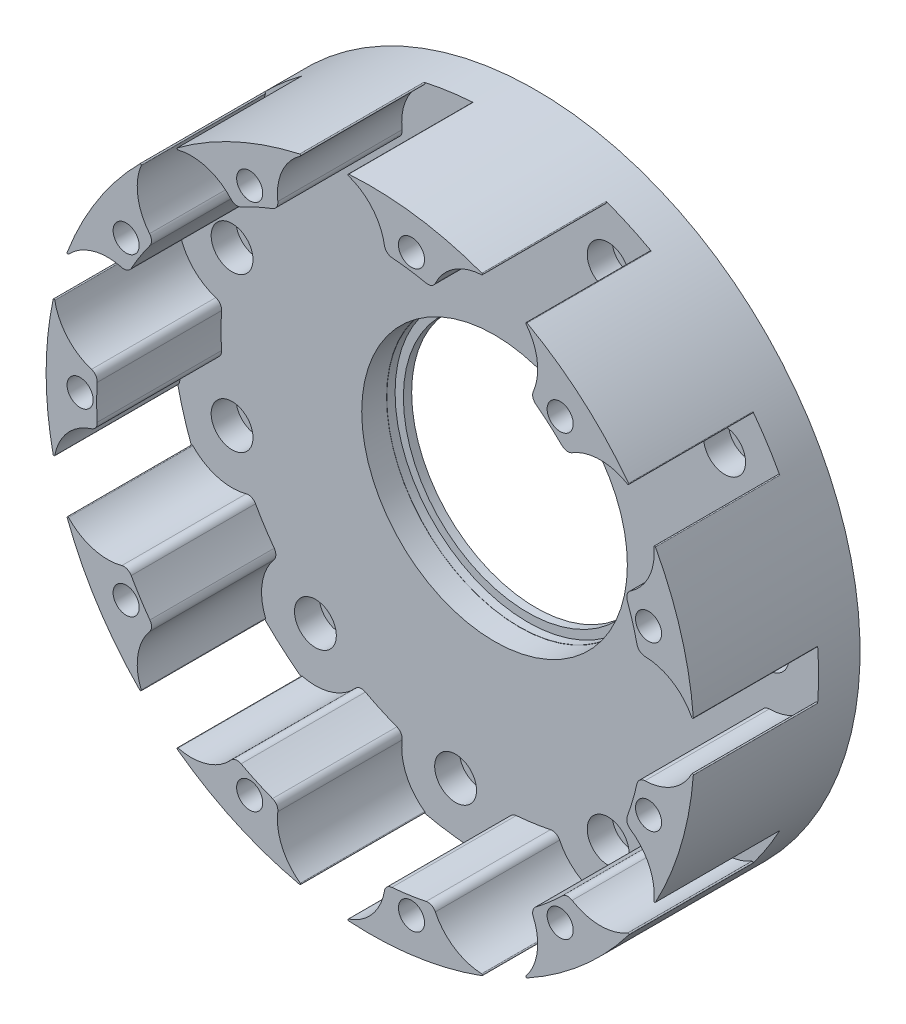
SolidWorks part; units mm, degrees
material "ABS"
ref_plane "Front Plane" through (0, 0, 0) normal (0, 0, 1) x (1, 0, 0)
ref_plane "Top Plane" through (0, 0, 0) normal (0, 1, 0) x (1, 0, 0)
ref_plane "Right Plane" through (0, 0, 0) normal (1, 0, 0) x (0, 0, -1)
sketch "Sketch1" plane through (0, 0, 0) normal (0, 0, 1) x (1, 0, 0)
  circle A0 centre (0, 0) radius 39.1
  circle A1 centre (0, 0) radius 33 construction
  circle A2 centre (33, 0) radius 2.525
  circle A3 centre (27.7614, -17.8411) radius 2.525
  circle A4 centre (13.7087, -30.0179) radius 2.525
  circle A5 centre (-4.6964, -32.6641) radius 2.525
  circle A6 centre (-21.6104, -24.9397) radius 2.525
  circle A7 centre (-31.6633, -9.2972) radius 2.525
  circle A8 centre (-31.6633, 9.2972) radius 2.525
  circle A9 centre (-21.6104, 24.9397) radius 2.525
  circle A10 centre (-4.6964, 32.6641) radius 2.525
  circle A11 centre (13.7087, 30.0179) radius 2.525
  circle A12 centre (27.7614, 17.8411) radius 2.525
  circle A13 centre (0, 0) radius 16.025
  point P28 (0, 0)
extrude "Boss-Extrude1" add sketch "Sketch1" along normal blind 3
sketch "Sketch2" plane through (0, 0, 0) normal (0, 0, -1) x (-1, 0, 0)
  circle A0 centre (0, 0) radius 16
  circle A1 centre (0, 0) radius 39.1
  circle A2 centre (0, 0) radius 39.1 construction
  dimension "D1" = 32
extrude "Boss-Extrude2" add sketch "Sketch2" along normal blind 2 contours A1 | A0
sketch "Sketch3" plane through (0, 0, 3) normal (0, 0, 1) x (1, 0, 0)
  circle A0 centre (33, 0) radius 1.6
  circle A1 centre (27.7614, -17.8411) radius 1.6
  circle A2 centre (13.7087, -30.0179) radius 1.6
  circle A3 centre (-4.6964, -32.6641) radius 1.6
  circle A4 centre (-21.6104, -24.9397) radius 1.6
  circle A5 centre (-31.6633, -9.2972) radius 1.6
  circle A6 centre (-31.6633, 9.2972) radius 1.6
  circle A7 centre (-21.6104, 24.9397) radius 1.6
  circle A8 centre (-4.6964, 32.6641) radius 1.6
  circle A9 centre (13.7087, 30.0179) radius 1.6
  circle A10 centre (27.7614, 17.8411) radius 1.6
  point P25 (0, 0)
  dimension "D1" = 3.2
  dimension "D2" = 11
sketch "Sketch4" plane through (0, 0, -2) normal (0, 0, -1) x (-1, 0, 0)
  circle A0 centre (0, 0) radius 16
  circle A1 centre (0, 0) radius 15
  dimension "D1" = 32
  dimension "D2" = 30
extrude "Boss-Extrude3" add sketch "Sketch4" against normal blind 1
sketch "Sketch5" plane through (0, 0, 3) normal (0, 0, 1) x (1, 0, 0)
  circle A0 centre (0, 0) radius 39.1
  circle A1 centre (0, 0) radius 39.1 construction
  arc A2 (1.7973, 32.951) -> (-11.0078, 31.1099) centre (-4.6964, 32.6641) ccw
  arc A3 (19.3266, 26.7485) -> (7.5589, 32.1226) centre (13.7087, 30.0179) ccw
  arc A4 (30.7199, 12.0535) -> (23.7258, 22.9366) centre (27.7614, 17.8411) ccw
  arc A5 (32.3598, -6.4684) -> (32.3598, 6.4684) centre (33, 0) ccw
  arc A6 (23.7258, -22.9366) -> (30.7199, -12.0535) centre (27.7614, -17.8411) ccw
  arc A7 (7.5589, -32.1226) -> (19.3266, -26.7485) centre (13.7087, -30.0179) ccw
  arc A8 (-11.0078, -31.1099) -> (1.7973, -32.951) centre (-4.6964, -32.6641) ccw
  arc A9 (-26.0797, -20.22) -> (-16.3027, -28.6918) centre (-21.6104, -24.9397) ccw
  arc A10 (-32.8714, -2.9104) -> (-29.2267, -15.3232) centre (-31.6633, -9.2972) ccw
  arc A11 (-29.2267, 15.3232) -> (-32.8714, 2.9104) centre (-31.6633, 9.2972) ccw
  arc A12 (-16.3027, 28.6918) -> (-26.0797, 20.22) centre (-21.6104, 24.9397) ccw
  arc A13 (-32.8714, 2.9104) -> (-32.8714, -2.9104) centre (0, 0) ccw
  arc A14 (-26.0797, 20.22) -> (-29.2267, 15.3232) centre (0, 0) ccw
  arc A15 (-11.0078, 31.1099) -> (-16.3027, 28.6918) centre (0, 0) ccw
  arc A16 (7.5589, 32.1226) -> (1.7973, 32.951) centre (0, 0) ccw
  arc A17 (23.7258, 22.9366) -> (19.3266, 26.7485) centre (0, 0) ccw
  arc A18 (32.3598, 6.4684) -> (30.7199, 12.0535) centre (0, 0) ccw
  arc A19 (30.7199, -12.0535) -> (32.3598, -6.4684) centre (0, 0) ccw
  arc A20 (19.3266, -26.7485) -> (23.7258, -22.9366) centre (0, 0) ccw
  arc A21 (1.7973, -32.951) -> (7.5589, -32.1226) centre (0, 0) ccw
  arc A22 (-16.3027, -28.6918) -> (-11.0078, -31.1099) centre (0, 0) ccw
  arc A23 (-29.2267, -15.3232) -> (-26.0797, -20.22) centre (0, 0) ccw
  point P29 (0, 0)
  point P30 (0, 0)
  point P42 (0, 0)
  dimension "D1" = 11
  dimension "D2" = 6.5
extrude "Boss-Extrude4" add sketch "Sketch5" along normal blind 15 contours A17 A4 A0 A3 | A18 A5 A0 A4 | A19 A6 A0 A5 | A20 A7 A0 A6 | A21 A8 A0 A7 | A22 A9 A0 A8 | A23 A10 A0 A9 | A13 A11 A0 A10 | A14 A12 A0 A11 | A15 A2 A0 A12 | A16 A3 A0 A2 region at (34.9977, 10.2762, 3) region at (34.9977, -10.2762, 3) region at (23.8862, 27.5661, 3) region at (23.8862, -27.5661, 3) region at (5.191, 36.1039, 3) region at (5.191, -36.1039, 3) region at (-15.1523, 33.179, 3) region at (-15.1523, -33.179, 3) region at (-30.6849, 19.72, 3) region at (-30.6849, -19.72, 3) region at (-36.4752, 0, 3)
fillet "Fillet1" radius 0.1 22 edges at (-7.9713, 38.2788, 10.5) (-27.401, 27.8926, 10.5) (-23.7091, 31.0916, 10.5) (-36.7548, 13.3378, 10.5) (-38.131, 8.6507, 10.5) (-38.131, -8.6507, 10.5) (-36.7548, -13.3378, 10.5) (-27.401, -27.8926, 10.5) (-23.7091, -31.0916, 10.5) (-7.9713, -38.2788, 10.5) (-3.136, -38.974, 10.5) (13.9892, -36.5118, 10.5) (18.4328, -34.4825, 10.5) (31.5083, -23.1525, 10.5) (34.1493, -19.043, 10.5) (39.0236, -2.4425, 10.5) (34.1493, 19.043, 10.5) (39.0236, 2.4425, 10.5) (31.5083, 23.1525, 10.5) (18.4328, 34.4825, 10.5) (13.9892, 36.5118, 10.5) (-3.136, 38.974, 10.5)
fillet "Fillet2" radius 1 22 edges at (-11.0078, -31.1099, 10.5) (-16.3027, -28.6918, 10.5) (23.7258, -22.9366, 10.5) (19.3266, -26.7485, 10.5) (7.5589, -32.1226, 10.5) (1.7973, -32.951, 10.5) (-29.2267, -15.3232, 10.5) (-26.0797, -20.22, 10.5) (-32.8714, -2.9104, 10.5) (-32.8714, 2.9104, 10.5) (-26.0797, 20.22, 10.5) (-29.2267, 15.3232, 10.5) (-16.3027, 28.6918, 10.5) (-11.0078, 31.1099, 10.5) (30.7199, -12.0535, 10.5) (32.3598, -6.4684, 10.5) (32.3598, 6.4684, 10.5) (30.7199, 12.0535, 10.5) (23.7258, 22.9366, 10.5) (19.3266, 26.7485, 10.5) (7.5589, 32.1226, 10.5) (1.7973, 32.951, 10.5)
sketch "Sketch7" plane through (0, 0, -2) normal (0, 0, -1) x (-1, 0, 0)
  line L0 (0, 0) -> (35, 0) construction
  circle A0 centre (35, 0) radius 1.575
  circle A1 centre (29.4439, -18.9224) radius 1.575
  circle A2 centre (14.5395, -31.8371) radius 1.575
  circle A3 centre (-4.981, -34.6438) radius 1.575
  circle A4 centre (-22.9201, -26.4512) radius 1.575
  circle A5 centre (-33.5823, -9.8606) radius 1.575
  circle A6 centre (-33.5823, 9.8606) radius 1.575
  circle A7 centre (-22.9201, 26.4512) radius 1.575
  circle A8 centre (-4.981, 34.6438) radius 1.575
  circle A9 centre (14.5395, 31.8371) radius 1.575
  circle A10 centre (29.4439, 18.9224) radius 1.575
  point P5 (0, 0)
  point P6 (0, 0)
  point P26 (0, 0)
  point P27 (0, 0)
  point P28 (0, 0)
  point P29 (0, 0)
  point P30 (0, 0)
  point P31 (0, 0)
  dimension "D2" = 3.15
  dimension "D1" = 35
  dimension "D3" = 11
extrude "Cut-Extrude1" cut sketch "Sketch7" against normal through all
sketch "Sketch8" plane through (0, 0, -2) normal (0, 0, -1) x (-1, 0, 0)
  line L0 (32.2124, -20.7016) -> (32.3689, -17.4145)
  line L1 (38.2909, 0) -> (36.6454, 2.85)
  line L2 (36.6454, 2.85) -> (33.3546, 2.85)
  line L3 (33.3546, 2.85) -> (31.7091, 0)
  line L4 (31.7091, 0) -> (33.3546, -2.85)
  line L5 (33.3546, -2.85) -> (36.6454, -2.85)
  line L6 (36.6454, -2.85) -> (38.2909, 0)
  line L7 (32.3689, -17.4145) -> (29.6005, -15.6353)
  line L8 (29.6005, -15.6353) -> (26.6754, -17.1432)
  line L9 (26.6754, -17.1432) -> (26.5188, -20.4304)
  line L10 (26.5188, -20.4304) -> (29.2873, -22.2096)
  line L11 (29.2873, -22.2096) -> (32.2124, -20.7016)
  line L12 (15.9066, -34.8306) -> (17.8155, -32.1499)
  line L13 (17.8155, -32.1499) -> (16.4484, -29.1564)
  line L14 (16.4484, -29.1564) -> (13.1724, -28.8436)
  line L15 (13.1724, -28.8436) -> (11.2635, -31.5243)
  line L16 (11.2635, -31.5243) -> (12.6306, -34.5178)
  line L17 (12.6306, -34.5178) -> (15.9066, -34.8306)
  line L18 (-5.4494, -37.9012) -> (-2.3942, -36.678)
  line L19 (-2.3942, -36.678) -> (-1.9259, -33.4206)
  line L20 (-1.9259, -33.4206) -> (-4.5127, -31.3864)
  line L21 (-4.5127, -31.3864) -> (-7.5678, -32.6095)
  line L22 (-7.5678, -32.6095) -> (-8.0362, -35.8669)
  line L23 (-8.0362, -35.8669) -> (-5.4494, -37.9012)
  line L24 (-25.0752, -28.9383) -> (-21.8438, -29.5611)
  line L25 (-21.8438, -29.5611) -> (-19.6887, -27.074)
  line L26 (-19.6887, -27.074) -> (-20.765, -23.9641)
  line L27 (-20.765, -23.9641) -> (-23.9965, -23.3413)
  line L28 (-23.9965, -23.3413) -> (-26.1516, -25.8284)
  line L29 (-26.1516, -25.8284) -> (-25.0752, -28.9383)
  line L30 (-36.7398, -10.7878) -> (-34.3581, -13.0588)
  line L31 (-34.3581, -13.0588) -> (-31.2005, -12.1316)
  line L32 (-31.2005, -12.1316) -> (-30.4247, -8.9335)
  line L33 (-30.4247, -8.9335) -> (-32.8064, -6.6625)
  line L34 (-32.8064, -6.6625) -> (-35.964, -7.5897)
  line L35 (-35.964, -7.5897) -> (-36.7398, -10.7878)
  line L36 (-36.7398, 10.7878) -> (-35.964, 7.5897)
  line L37 (-35.964, 7.5897) -> (-32.8064, 6.6625)
  line L38 (-32.8064, 6.6625) -> (-30.4247, 8.9335)
  line L39 (-30.4247, 8.9335) -> (-31.2005, 12.1316)
  line L40 (-31.2005, 12.1316) -> (-34.3581, 13.0588)
  line L41 (-34.3581, 13.0588) -> (-36.7398, 10.7878)
  line L42 (-25.0752, 28.9383) -> (-26.1516, 25.8284)
  line L43 (-26.1516, 25.8284) -> (-23.9965, 23.3413)
  line L44 (-23.9965, 23.3413) -> (-20.765, 23.9641)
  line L45 (-20.765, 23.9641) -> (-19.6887, 27.074)
  line L46 (-19.6887, 27.074) -> (-21.8438, 29.5611)
  line L47 (-21.8438, 29.5611) -> (-25.0752, 28.9383)
  line L48 (-5.4494, 37.9012) -> (-8.0362, 35.8669)
  line L49 (-8.0362, 35.8669) -> (-7.5678, 32.6095)
  line L50 (-7.5678, 32.6095) -> (-4.5127, 31.3864)
  line L51 (-4.5127, 31.3864) -> (-1.9259, 33.4206)
  line L52 (-1.9259, 33.4206) -> (-2.3942, 36.678)
  line L53 (-2.3942, 36.678) -> (-5.4494, 37.9012)
  line L54 (15.9066, 34.8306) -> (12.6306, 34.5178)
  line L55 (12.6306, 34.5178) -> (11.2635, 31.5243)
  line L56 (11.2635, 31.5243) -> (13.1724, 28.8436)
  line L57 (13.1724, 28.8436) -> (16.4484, 29.1564)
  line L58 (16.4484, 29.1564) -> (17.8155, 32.1499)
  line L59 (17.8155, 32.1499) -> (15.9066, 34.8306)
  line L60 (32.2124, 20.7016) -> (29.2873, 22.2096)
  line L61 (29.2873, 22.2096) -> (26.5188, 20.4304)
  line L62 (26.5188, 20.4304) -> (26.6754, 17.1432)
  line L63 (26.6754, 17.1432) -> (29.6005, 15.6353)
  line L64 (29.6005, 15.6353) -> (32.3689, 17.4145)
  line L65 (32.3689, 17.4145) -> (32.2124, 20.7016)
  circle A0 centre (35, 0) radius 2.85 construction
  circle A1 centre (29.4439, -18.9224) radius 2.85 construction
  circle A2 centre (14.5395, -31.8371) radius 2.85 construction
  circle A3 centre (-4.981, -34.6438) radius 2.85 construction
  circle A4 centre (-22.9201, -26.4512) radius 2.85 construction
  circle A5 centre (-33.5823, -9.8606) radius 2.85 construction
  circle A6 centre (-33.5823, 9.8606) radius 2.85 construction
  circle A7 centre (-22.9201, 26.4512) radius 2.85 construction
  circle A8 centre (-4.981, 34.6438) radius 2.85 construction
  circle A9 centre (14.5395, 31.8371) radius 2.85 construction
  circle A10 centre (29.4439, 18.9224) radius 2.85 construction
  point P10 (0, 0)
  point P11 (0, 0)
  point P91 (0, 0)
  point P92 (0, 0)
  point P93 (0, 0)
  point P94 (0, 0)
  point P95 (-0.9223, -0.4876)
  point P96 (0, 0)
  dimension "D1" = 5.7
  dimension "D2" = 11
extrude "Cut-Extrude3" cut sketch "Sketch8" against normal blind 3
equation "\"RingPinShaft\"= 5.05"
equation "\"CenterBearingOut\"=32.05"
equation "\"OutputBearingOut\"=37.05"
equation "\"RingPostIn\"=5.15"
equation "\"CamBearingOut\"=15.1"
equation "\"DiskOutputShaft\"=10.1"
equation "\"CenterShaft\"=25.2"
equation "\"Eccentricity\"=2"
equation "\"CycCamShaft\"=10.05"
equation "\"m3Thru\"=3.15"
equation "\"m3Insert\"=4.2"
equation "\"MountingHoleDiam\"=35"
equation "\"D1@Sketch7\"=\"MountingHoleDiam\""
equation "\"D2@Sketch7\"=\"m3Thru\""
